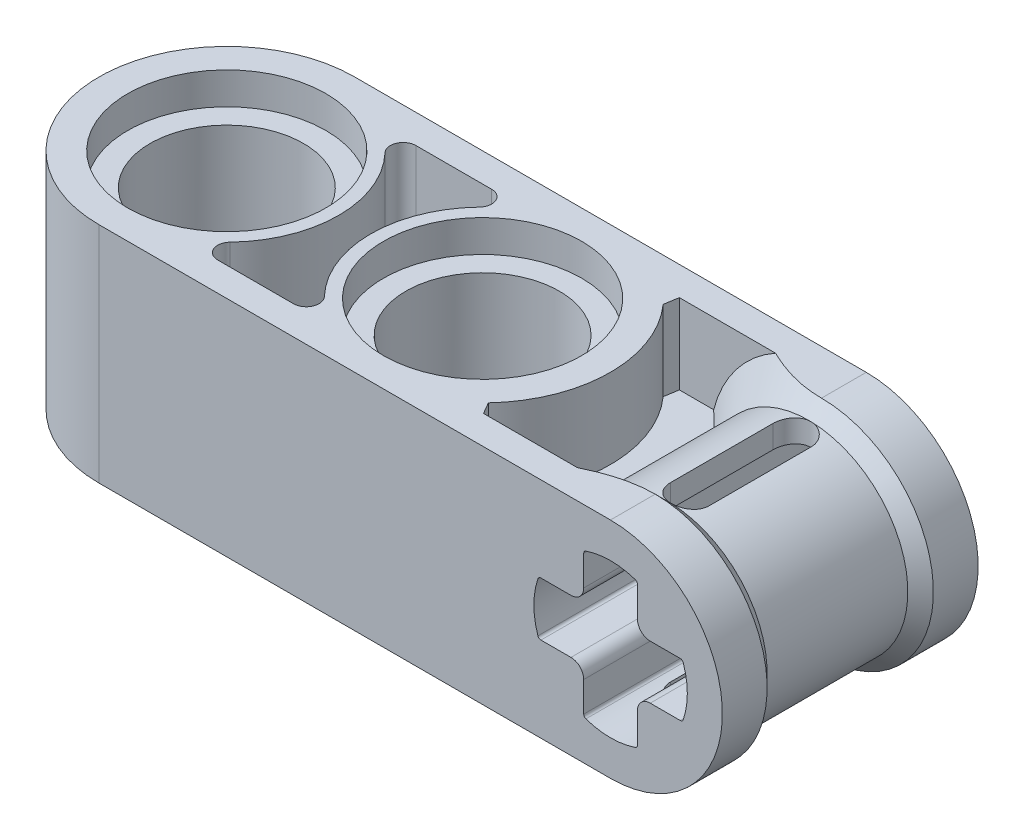
SolidWorks part; units mm, degrees
ref_plane "Front Plane" through (0, 0, 0) normal (0, 0, 1) x (1, 0, 0)
ref_plane "Top Plane" through (0, 0, 0) normal (0, 1, 0) x (1, 0, 0)
ref_plane "Right Plane" through (0, 0, 0) normal (1, 0, 0) x (0, 0, -1)
sketch "Sketch1" plane through (0, 0, 0) normal (0, 1, 0) x (1, 0, 0)
  circle A0 centre (0, 0) radius 4
  dimension "D1" = 8
extrude "Boss-Extrude1" add sketch "Sketch1" along normal mid plane 7
sketch "Sketch2" plane through (0, 0, 0) normal (1, 0, 0) x (0, 0, -1)
  line L1 (-4, 3.5) -> (4, 3.5)
  line L2 (-4, 3.5) -> (-4, -3.5)
  line L3 (-4, -3.5) -> (4, -3.5)
  line L4 (4, 3.5) -> (4, -3.5)
extrude "Boss-Extrude2" add sketch "Sketch2" along normal blind 8
sketch "Sketch3" plane through (0, 3.5, 0) normal (0, 1, 0) x (1, 0, 0)
  circle A0 centre (0, 0) radius 3.1
  dimension "D1" = 6.2
extrude "Cut-Extrude1" cut sketch "Sketch3" against normal blind 1
sketch "Sketch4" plane through (0, 2.5, 0) normal (0, 1, 0) x (1, 0, 0)
  circle A0 centre (0, 0) radius 2.4
  dimension "D1" = 4.8
extrude "Cut-Extrude2" cut sketch "Sketch4" against normal through all
sketch "Sketch5" plane through (0, 3.5, 0) normal (0, 1, 0) x (1, 0, 0)
  line L0 (8, 4) -> (8, -4) construction
  circle A0 centre (8, 0) radius 4
  dimension "D1" = 8
extrude "Boss-Extrude3" add sketch "Sketch5" against normal blind 7
sketch "Sketch6" plane through (0, 3.5, 0) normal (0, 1, 0) x (1, 0, 0)
  circle A0 centre (8, 0) radius 3.1
  dimension "D1" = 6.2
extrude "Cut-Extrude3" cut sketch "Sketch6" against normal blind 1
sketch "Sketch7" plane through (0, 2.5, 0) normal (0, 1, 0) x (1, 0, 0)
  circle A0 centre (8, 0) radius 2.4
  dimension "D1" = 4.8
extrude "Cut-Extrude4" cut sketch "Sketch7" against normal through all
mirror "Mirror2" about plane through (0, 0, 0) normal (0, 1, 0) of "Cut-Extrude1", "Cut-Extrude3"
sketch "Sketch9" plane through (0, 3.5, 0) normal (0, 1, 0) x (1, 0, 0)
  line L0 (2.8142, 3.1) -> (5.1858, 3.1)
  line L1 (2.8142, -3.1) -> (5.1858, -3.1)
  line L2 (8, 4) -> (0, 4) construction
  arc A0 (2.5256, -2.4231) -> (2.5256, 2.4231) centre (0, 0) ccw
  arc A1 (5.4744, 2.4231) -> (5.4744, -2.4231) centre (8, 0) ccw
  arc A6 (2.5256, -2.4231) -> (2.8142, -3.1) centre (2.8142, -2.7) ccw
  arc A7 (5.4744, -2.4231) -> (5.1858, -3.1) centre (5.1858, -2.7) cw
  arc A8 (5.4744, 2.4231) -> (5.1858, 3.1) centre (5.1858, 2.7) ccw
  arc A9 (2.5256, 2.4231) -> (2.8142, 3.1) centre (2.8142, 2.7) cw
  dimension "D1" = 7
  dimension "D2" = 7
  dimension "D3" = 0.4
extrude "Cut-Extrude5" cut sketch "Sketch9" against normal through all
sketch "Sketch10" plane through (0, 0, 0) normal (1, 0, 0) x (0, 0, -1)
  line L0 (-4, -3.5) -> (4, -3.5) construction
  line L1 (-4, 3.5) -> (-3.1, 3.5)
  line L2 (-4, 3.5) -> (-4, -3.5)
  line L3 (-4, -3.5) -> (-3.1, -3.5)
  line L4 (-3.1, 3.5) -> (-3.1, -3.5)
  dimension "D1" = 0.9
extrude "Boss-Extrude4" add sketch "Sketch10" along normal blind 16
sketch "Sketch11" plane through (0, 0, 4) normal (0, 0, 1) x (1, 0, 0)
  line L0 (16, 3.5) -> (16, -3.5) construction
  circle A0 centre (16, 0) radius 3.5
extrude "Boss-Extrude5" add sketch "Sketch11" against normal blind 0.9
sketch "Sketch15" plane through (0, 0, 4) normal (0, 0, 1) x (1, 0, 0)
  circle A0 centre (16, 0) radius 3.1
  dimension "D1" = 6.2
extrude "Boss-Extrude6" add sketch "Sketch15" against normal blind 8
mirror "Mirror3" about plane through (0, 0, 0) normal (0, 0, 1) of "Boss-Extrude4", "Boss-Extrude5"
sketch "Sketch20" plane through (0, 0, 0) normal (0, 1, 0) x (1, 0, 0)
  line L0 (10.5278, 3.1) -> (13.2639, 3.1)
  line L1 (16, 3.1) -> (10.5278, 3.1) construction
  line L2 (13.2639, 3.1) -> (13.2639, -3.1)
  line L3 (16, -3.1) -> (10.5278, -3.1) construction
  line L4 (13.2639, -3.1) -> (10.5278, -3.1)
  arc A0 (10.5278, 3.1) -> (10.5278, -3.1) centre (8, 0) cw
extrude "Boss-Extrude14" add sketch "Sketch20" along normal mid plane 2
sketch "Sketch21" plane through (0, 0, 4) normal (0, 0, 1) x (1, 0, 0)
  line L0 (15.1635, -1.2398) -> (15.1635, -2.1775)
  line L1 (15.1635, 2.1779) -> (15.1635, 1.2402)
  line L2 (16.8435, 2.1779) -> (16.8435, 1.2402)
  line L3 (15.1635, 2.2484) -> (16.8435, -2.248) construction
  line L4 (15.1635, -2.248) -> (16.8435, 2.2484) construction
  line L5 (13.8258, 0.8402) -> (14.7635, 0.8402)
  line L6 (13.8258, -0.8398) -> (14.7635, -0.8398)
  line L7 (13.7553, 0.8402) -> (18.2517, -0.8398) construction
  line L8 (13.7553, -0.8398) -> (18.2517, 0.8402) construction
  line L9 (17.2435, 0.8402) -> (18.1812, 0.8402)
  line L10 (16.8435, -1.2398) -> (16.8435, -2.1775)
  line L11 (17.2435, -0.8398) -> (18.1812, -0.8398)
  arc A1 (16.7757, 2.2726) -> (15.2313, 2.2726) centre (16.0035, 0.0002) ccw
  arc A2 (13.7311, 0.7724) -> (13.7311, -0.772) centre (16.0035, 0.0002) ccw
  arc A3 (18.2759, -0.772) -> (18.2759, 0.7724) centre (16.0035, 0.0002) ccw
  arc A4 (15.2313, -2.2722) -> (16.7757, -2.2722) centre (16.0035, 0.0002) ccw
  arc A5 (13.8258, 0.8402) -> (13.7311, 0.7724) centre (13.8258, 0.7402) ccw
  arc A6 (13.7311, -0.772) -> (13.8258, -0.8398) centre (13.8258, -0.7398) ccw
  arc A7 (15.1635, -2.1775) -> (15.2313, -2.2722) centre (15.2635, -2.1775) ccw
  arc A8 (16.7757, -2.2722) -> (16.8435, -2.1775) centre (16.7435, -2.1775) ccw
  arc A9 (18.1812, -0.8398) -> (18.2759, -0.772) centre (18.1812, -0.7398) ccw
  arc A10 (18.1812, 0.8402) -> (18.2759, 0.7724) centre (18.1812, 0.7402) cw
  arc A11 (16.7757, 2.2726) -> (16.8435, 2.1779) centre (16.7435, 2.1779) cw
  arc A12 (15.2313, 2.2726) -> (15.1635, 2.1779) centre (15.2635, 2.1779) ccw
  arc A13 (15.1635, -1.2398) -> (14.7635, -0.8398) centre (14.7635, -1.2398) ccw
  arc A14 (16.8435, -1.2398) -> (17.2435, -0.8398) centre (17.2435, -1.2398) cw
  arc A15 (17.2435, 0.8402) -> (16.8435, 1.2402) centre (17.2435, 1.2402) cw
  arc A16 (14.7635, 0.8402) -> (15.1635, 1.2402) centre (14.7635, 1.2402) ccw
  point P3 (0, 0)
extrude "Cut-Extrude7" cut sketch "Sketch21" against normal through all
chamfer "Chamfer1" distance 0.6 angle 60 2 edges at (10.5278, 2.25, 3.1) (10.5278, 2.25, -3.1) first distance on face at (13.7221, 0, 3.1) first distance on face at (11.2639, 2.25, 0)
chamfer "Chamfer2" distance 0.9 angle 45 2 edges at (19.1, 0, 3.1) (19.1, 0, -3.1)
sketch "Sketch24" plane through (0, 0, 0) normal (0, 1, 0) x (1, 0, 0)
  line L0 (16.0829, 1.6) -> (16.0829, -1.6) construction
  line L1 (16.6829, 1.6) -> (16.6829, -1.6)
  line L2 (15.4829, 1.6) -> (15.4829, -1.6)
  line L3 (13.0657, 2.2) -> (19.1, 2.2) construction
  line L4 (19.1, -2.2) -> (13.0657, -2.2) construction
  arc A0 (16.6829, 1.6) -> (15.4829, 1.6) centre (16.0829, 1.6) ccw
  arc A1 (15.4829, -1.6) -> (16.6829, -1.6) centre (16.0829, -1.6) ccw
  point P2 (16.0829, 0)
  point P9 (16.0829, -2.2)
  dimension "D1" = 1.2
extrude "Cut-Extrude9" cut sketch "Sketch24" against normal through all both and the other way through all
